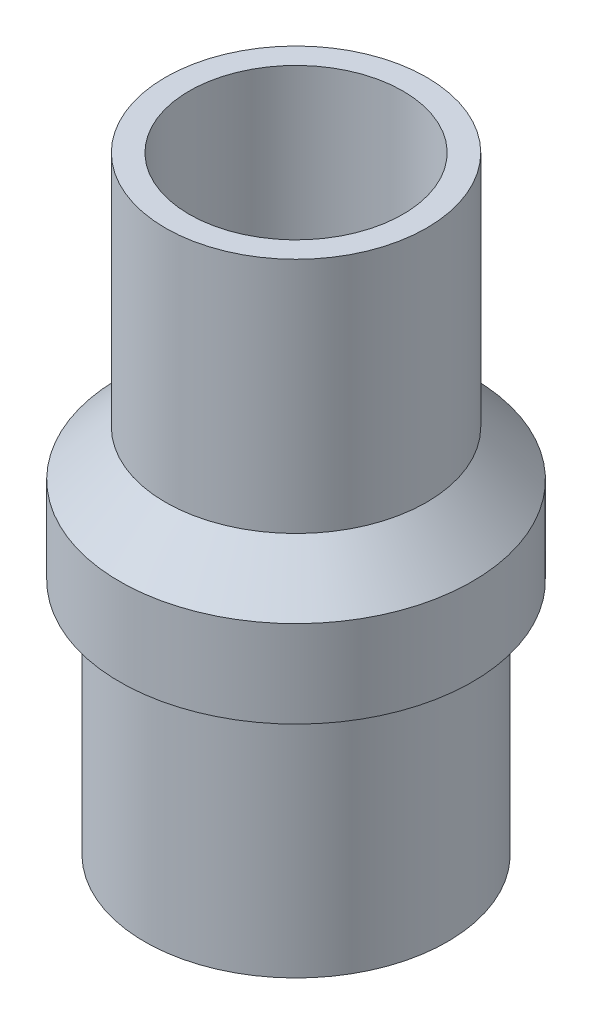
SolidWorks part; units mm, degrees
ref_plane "Front Plane" through (0, 0, 0) normal (0, 0, 1) x (1, 0, 0)
ref_plane "Top Plane" through (0, 0, 0) normal (0, 1, 0) x (1, 0, 0)
ref_plane "Right Plane" through (0, 0, 0) normal (1, 0, 0) x (0, 0, -1)
sketch "Sketch1" plane through (0, 0, 0) normal (0, 0, 1) x (1, 0, 0)
  line L0 (0, 0) -> (0, 26.8596) construction
  line L1 (12.85, 3.5) -> (9, 7.35)
  line L2 (14.85, 4.3284) -> (11, 8.1784)
  line L3 (14.85, 4.3284) -> (14.85, -3)
  line L4 (12.85, 3.5) -> (12.85, -3)
  line L5 (12.85, 8.225) -> (12.85, -3) construction
  line L6 (10.75, 0) -> (12.75, 0)
  line L7 (10.75, 0) -> (10.75, -23)
  line L8 (12.75, 0) -> (12.75, -1.5)
  line L9 (9, 28.1784) -> (9, 7.35)
  line L10 (11, 28.1784) -> (11, 8.1784)
  line L11 (14.2642, 4.9142) -> (8.7818, 10.3966) construction
  line L12 (9, 28.1784) -> (11, 28.1784)
  line L13 (9, 6.1541) -> (14.8742, 6.2252) construction
  line L14 (10.75, -23) -> (12.75, -23)
  line L15 (12.85, -3) -> (14.85, -3)
  line L16 (9, 28.1784) -> (9, 6.1541) construction
  line L17 (12.85, 3.5) -> (7.3676, 8.9824) construction
  line L18 (14.85, 8.225) -> (14.85, -3) construction
  line L19 (12.75, -3.1) -> (13.35, -3.1)
  line L20 (12.75, -23) -> (12.75, -3.8)
  line L21 (11, 8.1784) -> (14.85, 8.225) construction
  line L22 (13.35, -3.1) -> (13.35, -3.8)
  line L23 (13.35, -3.8) -> (12.75, -3.8)
  line L24 (12.75, -3.1) -> (12.75, -1.5)
  dimension "D2" = 11
  dimension "D3" = 20
  dimension "D4" = 135
  dimension "D5" = 2
  dimension "D6" = 3
  dimension "D8" = 0.1
  dimension "D9" = 2
  dimension "D10" = 3.5
  dimension "D11" = 12.75
  dimension "D7" = 20
  dimension "D13" = 2
  dimension "D14" = 0.1
  dimension "D15" = 0.6
  dimension "D16" = 0.8
  dimension "D12" = 2
revolve "Revolve1" add sketch "Sketch1" angle 360 about L0
sketch "Sketch3" plane through (0, 0, 0) normal (0, 1, 0) x (1, 0, 0)
  line L0 (0, 9) -> (0, 0) construction
  line L1 (-1.5, 8.8741) -> (-1.5, 2.5981)
  line L2 (0, 9) -> (0, 0) construction
  line L3 (1.5, 8.8741) -> (1.5, 2.5981)
  line L4 (8.4352, -3.138) -> (3, 0)
  line L5 (-1.5, 9) -> (-1.5, 0) construction
  line L6 (1.5, 9) -> (1.5, 0) construction
  line L7 (6.9352, -5.7361) -> (1.5, -2.5981)
  line L8 (-6.9352, -5.7361) -> (-1.5, -2.5981)
  line L9 (-8.4352, -3.138) -> (-3, 0)
  circle A5 centre (0, 0) radius 10.75 construction
  circle A6 centre (0, 0) radius 9 construction
  arc A7 (-1.5, 8.8741) -> (-8.4352, -3.138) centre (0, 0) ccw
  arc A8 (-1.5, 2.5981) -> (-3, 0) centre (0, 0) ccw
  circle A9 centre (0, 0) radius 1.25
  arc A10 (3, 0) -> (1.5, 2.5981) centre (0, 0) ccw
  arc A11 (-1.5, -2.5981) -> (1.5, -2.5981) centre (0, 0) ccw
  arc A12 (-6.9352, -5.7361) -> (6.9352, -5.7361) centre (0, 0) ccw
  arc A13 (8.4352, -3.138) -> (1.5, 8.8741) centre (0, 0) ccw
  circle A14 centre (0, 0) radius 10.75
  point P5 (1.5, 0)
  point P6 (-1.5, 0)
  point P7 (-1.5, -12)
  point P8 (1.5, 0)
  point P9 (1.5, -12)
  point P11 (1.5, 0)
  point P12 (1.5, 8.25)
  point P13 (-1.5, 0)
  point P14 (-1.5, 8.25)
  point P16 (1.5, 9)
  point P17 (-1.5, 0)
  point P18 (-1.5, 9)
  point P39 (0, 0)
  dimension "D3" = 6
  dimension "D1" = 1.5
  dimension "D4" = 2.5
  dimension "D2" = 1.5
extrude "Boss-Extrude1" add sketch "Sketch3" against normal blind 2 contours A13 L4 A10 L3 A12 L8 A11 L7 A9 L1 A8 L9 A7 region at (-10.4459, 0, 0)
sketch "Sketch5" plane through (0, 0, 0) normal (0, 0, 1) x (1, 0, 0)
  line L0 (0, 0) -> (0, 3.6213) construction
  line L2 (-1.25, 0.5) -> (-1.25, -2.2)
  line L3 (-1.25, -2.2) -> (-3, -2.2)
  line L4 (-3, -2.2) -> (-3, -3.7)
  line L5 (-3, -3.7) -> (0, -3.7)
  line L6 (0, -3.7) -> (0, 0.5)
  line L7 (0, 0.5) -> (-1.25, 0.5)
  line L9 (-9, -2) -> (-1.5, -2) construction
  dimension "D1" = 1.25
  dimension "D2" = 0.5
  dimension "D3" = 0.2
  dimension "D4" = 1.5
  dimension "D5" = 3
revolve "Revolve2" add sketch "Sketch5" angle 360 about L0
fillet "Fillet1" radius 0.6 1 edges at (0, -3.1, -12.75)
